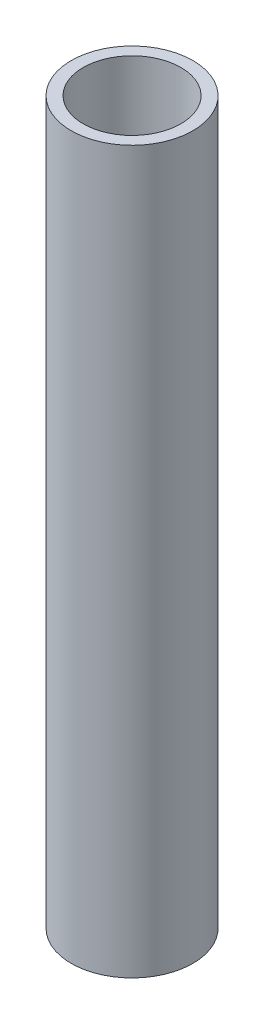
SolidWorks part; units mm, degrees
ref_plane "Front Plane" through (0, 0, 0) normal (0, 0, 1) x (1, 0, 0)
ref_plane "Top Plane" through (0, 0, 0) normal (0, 1, 0) x (1, 0, 0)
ref_plane "Right Plane" through (0, 0, 0) normal (1, 0, 0) x (0, 0, -1)
sketch "Sketch1" plane through (0, 0, 0) normal (0, 1, 0) x (1, 0, 0)
  circle A0 centre (0, 0) radius 4.05
  circle A1 centre (0, 0) radius 3.25
  dimension "D1" = 6.5
  dimension "D2" = 0.8
sketch "Sketch2" plane through (0, 0, 0) normal (0, 1, 0) x (1, 0, 0)
  circle A0 centre (0, 0) radius 3.25 construction
  circle A1 centre (0, 0) radius 4.05 construction
  circle A2 centre (0, 0) radius 3.25
  circle A3 centre (0, 0) radius 4.05
extrude "Boss-Extrude1" add sketch "Sketch2" along normal up to surface (48 mm away)
